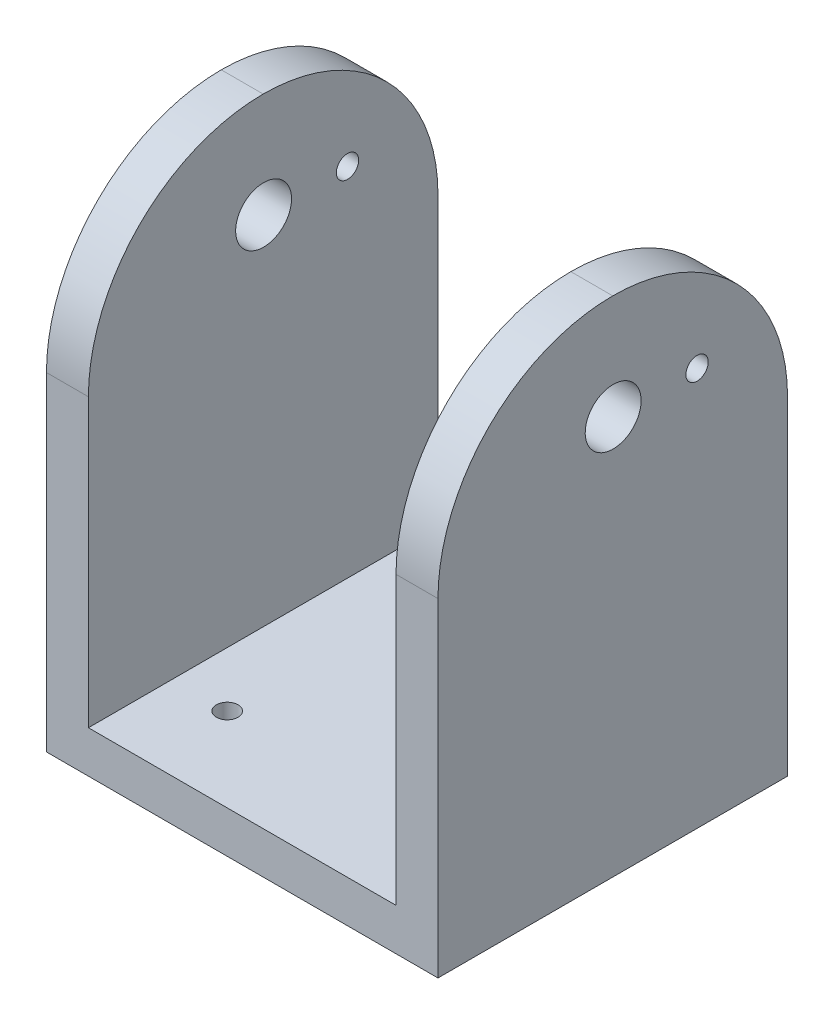
SolidWorks part; units mm, degrees
ref_plane "Front" through (0, 0, 0) normal (0, 0, 1) x (1, 0, 0)
ref_plane "Top" through (0, 0, 0) normal (0, 1, 0) x (1, 0, 0)
ref_plane "Right" through (0, 0, 0) normal (1, 0, 0) x (0, 0, -1)
sketch "Sketch1" plane through (0, 0, 0) normal (0, 0, 1) x (1, 0, 0)
  line L1 (-22, -20) -> (22, -20) construction
  line L2 (-22, -20) -> (-22, 20) construction
  line L3 (-22, 20) -> (22, 20) construction
  line L4 (22, -20) -> (22, 20) construction
  line L5 (-22, -20) -> (22, 20) construction
  line L6 (-22, 20) -> (22, -20) construction
  line L7 (22, -27) -> (28, -27)
  line L8 (22, -27) -> (22, 45)
  line L9 (22, 45) -> (28, 45)
  line L10 (28, -27) -> (28, 45)
  line L11 (22, -27) -> (28, 45) construction
  line L12 (22, 45) -> (28, -27) construction
  line L13 (-28, -27) -> (-22, -27)
  line L14 (-28, -27) -> (-28, 45)
  line L15 (-28, 45) -> (-22, 45)
  line L16 (-22, -27) -> (-22, 45)
  line L17 (-28, -27) -> (-22, 45) construction
  line L18 (-28, 45) -> (-22, -27) construction
  line L19 (-28, -21) -> (28, -21)
  line L20 (-28, -21) -> (-28, -27)
  line L21 (-28, -27) -> (28, -27)
  line L22 (28, -21) -> (28, -27)
  line L23 (-28, -21) -> (28, -27) construction
  line L24 (-28, -27) -> (28, -21) construction
  point P0 (0, 0)
  point P5 (25, 9)
  point P11 (-25, 9)
  point P20 (0, -24)
  dimension "D1" = 40
  dimension "D2" = 44
  dimension "D3" = 72
  dimension "D4" = 1
  dimension "D7" = 72
  dimension "D8" = 6
  dimension "D9" = 6
  dimension "D10" = 6
extrude "Boss-Extrude1" add sketch "Sketch1" along normal blind 50 contours L14 L19 L16 L15 | L16 L21 L8 L19 | L19 L14 L13 L16 | L19 L8 L7 L10 | L8 L19 L10 L9 region at (25, -24, 0) region at (0, -24, 0) region at (25, 12, 0) region at (-25, -24, 0) region at (-25, 12, 0)
fillet "Fillet1" radius 25 4 edges at (-25, 45, 50) (-25, 45, 0) (25, 45, 0) (25, 45, 50)
sketch "Sketch2" plane through (28, 0, 0) normal (1, 0, 0) x (0, 0, -1)
  line L0 (-25, 20) -> (-25, 38) construction
  circle A0 centre (-25, 20) radius 12.5
  circle A1 centre (-25, 38) radius 2
  circle A2 centre (0.9808, 35) radius 2
  circle A3 centre (11.3731, 11) radius 2
  circle A4 centre (-4.2154, -10) radius 2
  circle A5 centre (-30.1962, -7) radius 2
  circle A6 centre (-40.5885, 17) radius 2
  point P18 (-14.6077, 14)
  dimension "D1" = 25
  dimension "D3" = 4
  dimension "D2" = 18
  dimension "D4" = 6
extrude "Cut-Extrude1" [suppressed] cut sketch "Sketch2" against normal through all
sketch "Sketch3" plane through (28, 0, 0) normal (1, 0, 0) x (0, 0, -1)
  line L0 (-50, -27) -> (0, -27) construction
  line L2 (-45.9412, 30) -> (-3.9412, 30) construction
  line L3 (-45.9412, 27) -> (-3.9412, 27)
  line L4 (-25, -27) -> (-24.9412, 30) construction
  line L5 (-45.9412, 27) -> (-45.9412, 33)
  line L6 (-45.9412, 33) -> (-3.9412, 33)
  line L7 (-3.9412, 27) -> (-3.9412, 33)
  line L9 (-45.9412, 27) -> (-3.9412, 33) construction
  line L10 (-45.9412, 33) -> (-3.9412, 27) construction
  circle A1 centre (-12.9412, 30) radius 1.6
  circle A2 centre (-24.9412, 30) radius 4
  dimension "D6" = 3.2
  dimension "D8" = 8
  dimension "D1" = 6
  dimension "D3" = 57
  dimension "D2" = 42
  dimension "D7" = 12
extrude "Cut-Extrude2" cut sketch "Sketch3" against normal through all contours A1 | A2 region at (28, 30, 12.9412)
sketch "Sketch4" plane through (0, -21, 0) normal (0, 1, 0) x (1, 0, 0)
  line L0 (0, -66.2843) -> (-79.6283, 13.344) construction
  line L1 (0, -66.2843) -> (0, 61.2817) construction
  line L2 (0, -66.2843) -> (71.4176, 5.1333) construction
  line L3 (14.1421, -52.1421) -> (-65.4861, 27.4861) construction
  line L4 (0, -38) -> (57.2754, 19.2754) construction
  line L6 (-14.1421, -52.1421) -> (57.2754, 19.2754) construction
  line L7 (-21.2132, -45.0711) -> (-7.0711, -30.9289) construction
  line L8 (21.2132, -45.0711) -> (7.0711, -30.9289) construction
  line L9 (-22, -50) -> (22, -50) construction
  circle A0 centre (-14.1421, -38) radius 1.55
  circle A1 centre (14.1421, -38) radius 1.55
  circle A2 centre (0, -13) radius 1.55
  dimension "D4" = 3.1
  dimension "D5" = 3.1
  dimension "D9" = 3.1
  dimension "D1" = 45
  dimension "D2" = 20
  dimension "D6" = 30
  dimension "D7" = 10
  dimension "D8" = 12
  dimension "D10" = 25
  dimension "D3" = 20
extrude "Cut-Extrude3" cut sketch "Sketch4" against normal through all
